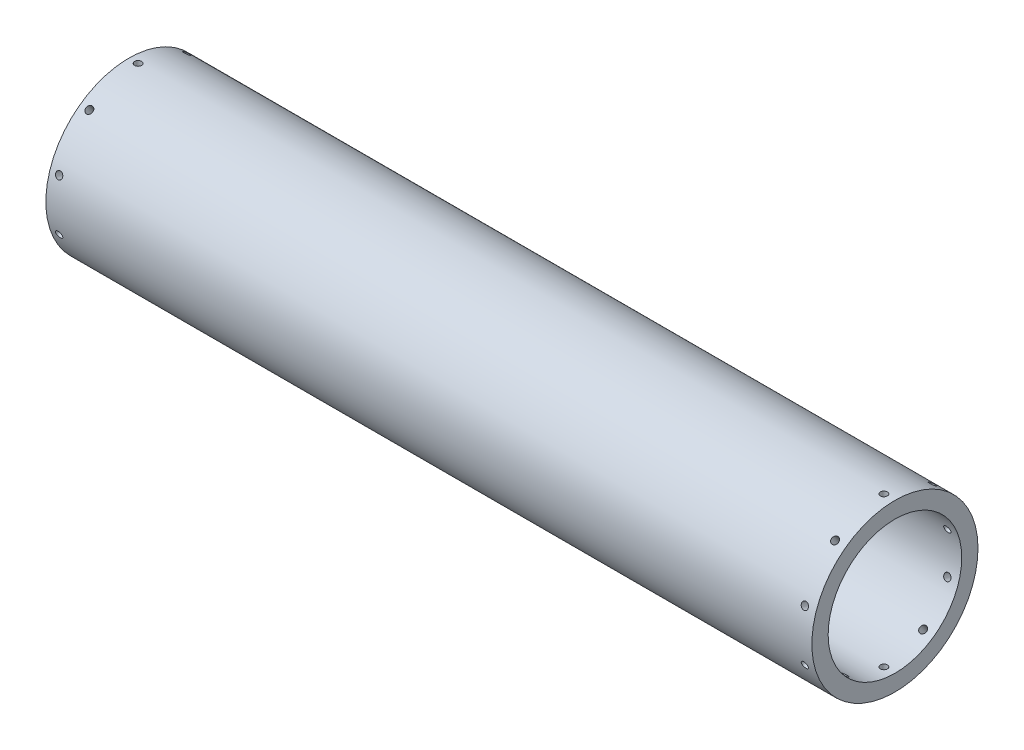
SolidWorks part; units mm, degrees
material "7075-T6 (SN)"
ref_plane "Front Plane" through (0, 0, 0) normal (0, 0, 1) x (1, 0, 0)
ref_plane "Top Plane" through (0, 0, 0) normal (0, 1, 0) x (1, 0, 0)
ref_plane "Right Plane" through (0, 0, 0) normal (1, 0, 0) x (0, 0, -1)
sketch "Sketch1" plane through (0, 0, 0) normal (1, 0, 0) x (0, 0, -1)
  circle A0 centre (0, 0) radius 45.9486
  circle A1 centre (0, 0) radius 57.15
  dimension "D1" = 91.8972
  dimension "D2" = 114.3
extrude "Boss-Extrude1" add sketch "Sketch1" along normal blind 527.05
sketch "Sketch2" plane through (0, 0, 0) normal (-1, 0, 0) x (0, 0, 1)
  circle A0 centre (0, 0) radius 44.577
  circle A1 centre (0, 0) radius 45.9486
  dimension "D1" = 89.154
extrude "Boss-Extrude2" add sketch "Sketch2" against normal blind 88.9
sketch "Sketch4" plane through (0, 0, 0) normal (0, 0, 1) x (1, 0, 0)
  line L0 (0, 0) -> (0, 88.0135) construction
  line L1 (0, 57.15) -> (0, -57.15) construction
  line L2 (0, -62.865) -> (0, 62.865) construction
ref_plane "Plane1" through (0, 57.15, 0) normal (0, 1, 0) x (1, 0, 0)
sketch "Sketch6" plane through (0, 57.15, 0) normal (0, 1, 0) x (1, 0, 0)
  line L0 (0, 57.15) -> (0, -57.15) construction
  circle A0 centre (6.35, 0) radius 2.413
  dimension "D1" = 4.826
  dimension "D2" = 6.35
extrude "Cut-Extrude1" cut sketch "Sketch6" against normal blind 15.24
pattern_circular "CirPattern1" count 10 every 36 about axis through (0, 0, 0) along (-1, 0, 0) of "Cut-Extrude1"
sketch "Sketch7" plane through (0, 57.15, 0) normal (0, 1, 0) x (1, 0, 0)
  line L0 (527.05, -57.15) -> (527.05, 57.15) construction
  circle A0 centre (519.43, 0) radius 2.413
  dimension "D2" = 4.826
  dimension "D1" = 7.62
extrude "Cut-Extrude2" cut sketch "Sketch7" against normal blind 15.24
pattern_circular "CirPattern2" count 10 every 36 about axis through (527.05, 0, 0) along (1, 0, 0) of "Cut-Extrude2"
